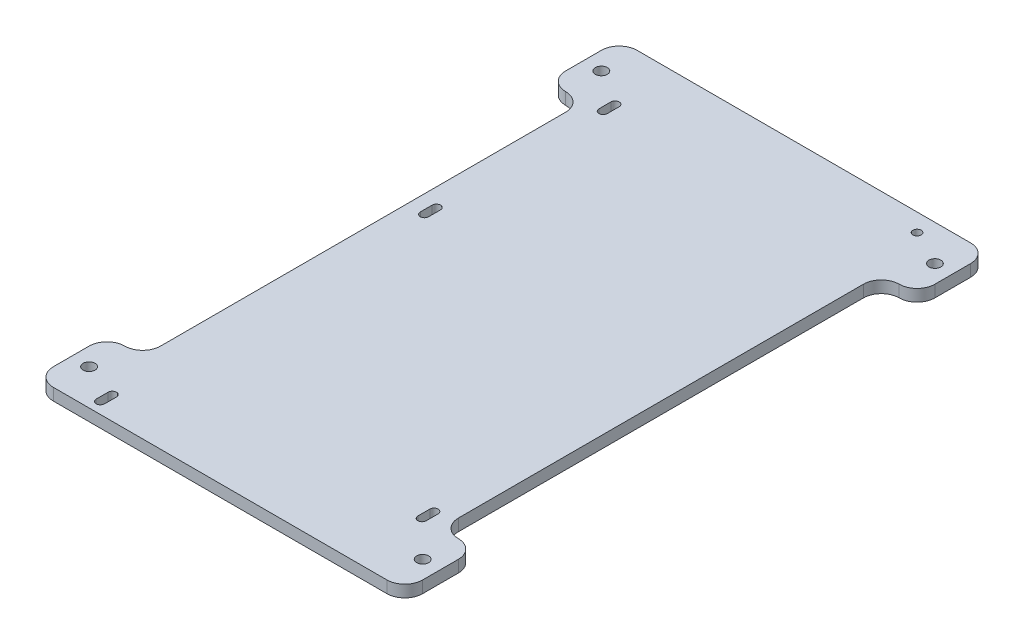
SolidWorks part; units mm, degrees
ref_plane "Front Plane" through (0, 0, 0) normal (0, 0, 1) x (1, 0, 0)
ref_plane "Top Plane" through (0, 0, 0) normal (0, 1, 0) x (1, 0, 0)
ref_plane "Right Plane" through (0, 0, 0) normal (1, 0, 0) x (0, 0, -1)
sketch "Sketch1" plane through (0, 0, 0) normal (0, 1, 0) x (1, 0, 0)
  line L1 (-70.9985, 131.6967) -> (54.0015, 131.6967)
  line L2 (-70.9985, 131.6967) -> (-70.9985, -113.3033)
  line L3 (-70.9985, -113.3033) -> (54.0015, -113.3033)
  line L4 (54.0015, 131.6967) -> (54.0015, -113.3033)
  dimension "D1" = 245
  dimension "D2" = 125
extrude "Boss-Extrude1" add sketch "Sketch1" along normal blind 5
sketch "Sketch2" plane through (0, 5, 0) normal (0, 1, 0) x (1, 0, 0)
  line L6 (54.0015, 131.6967) -> (69.0015, 131.6967)
  line L7 (54.0015, 131.6967) -> (54.0015, 101.6967)
  line L8 (54.0015, 101.6967) -> (69.0015, 101.6967)
  line L9 (69.0015, 131.6967) -> (69.0015, 101.6967)
  line L10 (-70.9985, 131.6967) -> (-85.9985, 131.6967)
  line L11 (-70.9985, 131.6967) -> (-70.9985, 101.6967)
  line L12 (-70.9985, 101.6967) -> (-85.9985, 101.6967)
  line L13 (-85.9985, 131.6967) -> (-85.9985, 101.6967)
  line L14 (-70.9985, -113.3033) -> (-85.9985, -113.3033)
  line L15 (-70.9985, -113.3033) -> (-70.9985, -83.3033)
  line L16 (-70.9985, -83.3033) -> (-85.9985, -83.3033)
  line L17 (-85.9985, -113.3033) -> (-85.9985, -83.3033)
  line L18 (54.0015, -113.3033) -> (69.0015, -113.3033)
  line L19 (54.0015, -113.3033) -> (54.0015, -83.3033)
  line L20 (54.0015, -83.3033) -> (69.0015, -83.3033)
  line L21 (69.0015, -113.3033) -> (69.0015, -83.3033)
  point P0 (0, 0)
  point P45 (46.5015, -97.9019)
  dimension "D1" = 15
  dimension "D8" = 30
extrude "Boss-Extrude2" add sketch "Sketch2" against normal blind 5
sketch "Sketch3" plane through (0, 0, 0) normal (0, -1, 0) x (1, 0, 0)
  line L0 (-85.9985, -131.6967) -> (-85.9985, -101.6967) construction
  line L1 (-85.9985, 83.3033) -> (-85.9985, 113.3033) construction
  line L2 (-70.9985, 83.3033) -> (-85.9985, 83.3033) construction
  line L3 (-85.9985, -131.6967) -> (-85.9985, -101.6967)
  line L4 (-85.9985, 83.3033) -> (-85.9985, 113.3033)
  line L5 (-70.9985, 83.3033) -> (-85.9985, 83.3033)
  line L6 (54.0015, -101.6967) -> (69.0015, -101.6967) construction
  line L7 (54.0015, -101.6967) -> (69.0015, -101.6967)
  circle A0 centre (-78.4985, 98.3033) radius 2.5
  circle A1 centre (61.5015, 98.3033) radius 2.5
  circle A2 centre (61.5015, -116.6967) radius 2.5
  circle A3 centre (-78.4985, -116.6967) radius 2.5
  point P13 (0, 0)
  point P14 (-78.4985, 83.3033)
  point P15 (0, 0)
  point P16 (-85.9985, 98.3033)
  point P17 (0, 0)
  point P18 (0, 0)
  point P19 (-85.9985, -116.6967)
  point P22 (0, 0)
  point P23 (61.5015, -101.6967)
  point P24 (0, 0)
  dimension "D1" = 5
extrude "Cut-Extrude1" cut sketch "Sketch3" against normal through all contours A0 | A1 | A3 | A2 region at (-78.4985, 0, 98.3033) region at (61.5015, 0, 98.3033) region at (61.5015, 0, -116.6967) region at (-78.4985, 0, -116.6967)
sketch "Sketch4" plane through (0, 5, 0) normal (0, 1, 0) x (1, 0, 0)
  line L0 (69.0015, 131.6967) -> (-85.9985, 131.6967) construction
  line L1 (54.0015, 124.1967) -> (46.5015, 124.1967) construction
  line L2 (54.0015, -83.3033) -> (54.0015, 101.6967) construction
  line L3 (-70.9985, 104.1967) -> (-63.4985, 104.1967) construction
  line L4 (-70.9985, 101.6967) -> (-70.9985, -83.3033) construction
  line L5 (46.5015, -83.5533) -> (46.5015, -78.5533) construction
  line L6 (44.7515, -83.5533) -> (44.7515, -78.5533)
  line L7 (48.2515, -83.5533) -> (48.2515, -78.5533)
  line L8 (-63.4985, -108.5533) -> (-63.4985, -103.5533) construction
  line L9 (-65.2485, -108.5533) -> (-65.2485, -103.5533)
  line L10 (-61.7485, -108.5533) -> (-61.7485, -103.5533)
  line L11 (-63.4985, 27.4467) -> (-63.4985, 32.4467) construction
  line L12 (-65.2485, 27.4467) -> (-65.2485, 32.4467)
  line L13 (-61.7485, 27.4467) -> (-61.7485, 32.4467)
  line L14 (-63.4985, 102.4467) -> (-63.4985, 107.4467) construction
  line L15 (-65.2485, 102.4467) -> (-65.2485, 107.4467)
  line L16 (-61.7485, 102.4467) -> (-61.7485, 107.4467)
  circle A0 centre (-63.4985, 104.1967) radius 1.75 construction
  circle A1 centre (46.5015, 124.1967) radius 1.75
  circle A2 centre (46.5015, -81.8033) radius 1.75 construction
  circle A3 centre (-63.4985, 29.1967) radius 1.75 construction
  circle A4 centre (-63.4985, -106.8033) radius 1.75 construction
  arc A5 (44.7515, -83.5533) -> (48.2515, -83.5533) centre (46.5015, -83.5533) ccw
  arc A6 (48.2515, -78.5533) -> (44.7515, -78.5533) centre (46.5015, -78.5533) ccw
  arc A7 (-65.2485, -108.5533) -> (-61.7485, -108.5533) centre (-63.4985, -108.5533) ccw
  arc A8 (-61.7485, -103.5533) -> (-65.2485, -103.5533) centre (-63.4985, -103.5533) ccw
  arc A9 (-65.2485, 27.4467) -> (-61.7485, 27.4467) centre (-63.4985, 27.4467) ccw
  arc A10 (-61.7485, 32.4467) -> (-65.2485, 32.4467) centre (-63.4985, 32.4467) ccw
  arc A11 (-65.2485, 102.4467) -> (-61.7485, 102.4467) centre (-63.4985, 102.4467) ccw
  arc A12 (-61.7485, 107.4467) -> (-65.2485, 107.4467) centre (-63.4985, 107.4467) ccw
  point P13 (46.5015, -81.0533)
  point P17 (50.2515, 124.1967)
  point P24 (-63.4985, -106.0533)
  point P33 (-63.4985, 29.9467)
  point P42 (-63.4985, 104.9467)
  point P47 (-63.4985, -97.7721)
  point P48 (-63.4985, -108.5533)
  point P49 (46.5015, -83.5533)
  point P50 (-63.4985, 27.4467)
  point P51 (-63.4985, 102.4467)
  point P52 (-63.4985, 108.5715)
  dimension "D2" = 3.5
  dimension "D1" = 7.5
  dimension "D3" = 110
  dimension "D4" = 136
  dimension "D5" = 75
  dimension "D6" = 20
  dimension "D7" = 206
  dimension "D8" = 5
  dimension "D9" = 5
  dimension "D10" = 5
  dimension "D11" = 5
extrude "Cut-Extrude2" cut sketch "Sketch4" against normal through all
fillet "Fillet4" radius 7.5 12 edges at (-70.9985, 2.5, 83.3033) (-85.9985, 2.5, 83.3033) (-85.9985, 2.5, 113.3033) (69.0015, 2.5, 113.3033) (69.0015, 2.5, 83.3033) (54.0015, 2.5, 83.3033) (54.0015, 2.5, -101.6967) (69.0015, 2.5, -101.6967) (69.0015, 2.5, -131.6967) (-85.9985, 2.5, -131.6967) (-70.9985, 2.5, -101.6967) (-85.9985, 2.5, -101.6967)
